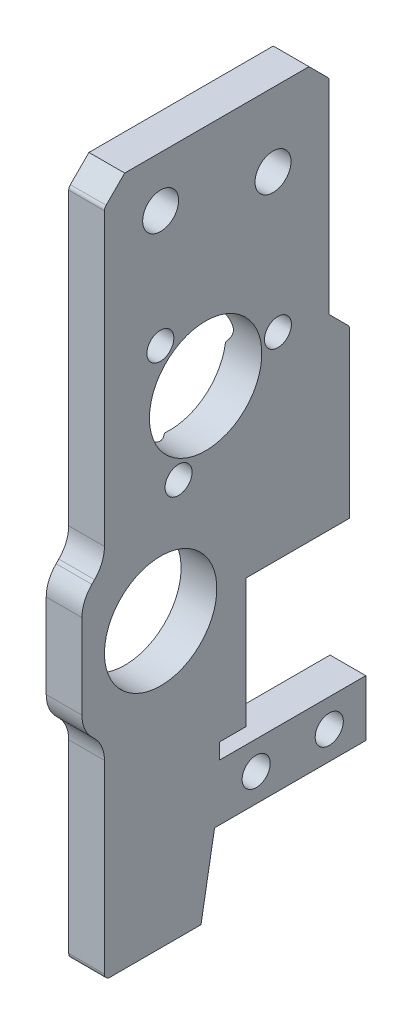
SolidWorks part; units mm, degrees
ref_plane "Front Plane" through (0, 0, 0) normal (0, 0, 1) x (1, 0, 0)
ref_plane "Top Plane" through (0, 0, 0) normal (0, 1, 0) x (1, 0, 0)
ref_plane "Right Plane" through (0, 0, 0) normal (1, 0, 0) x (0, 0, -1)
sketch "Sketch1" plane through (0, 0, 0) normal (1, 0, 0) x (0, 0, -1)
  line L0 (0, 0) -> (0, 18.2)
  line L1 (0, 18.2) -> (-2, 20.2)
  line L2 (-2, 20.2) -> (-2, 30.2)
  line L3 (-2, 30.2) -> (0, 32.2)
  line L4 (0, 32.2) -> (0, 61.31)
  line L5 (0, 61.31) -> (20, 61.31)
  line L7 (21.8, 24.71) -> (12.6, 24.71)
  line L8 (10.25, 13.26) -> (10.25, 11.86)
  line L9 (10.25, 11.86) -> (23.25, 11.86)
  line L10 (23.25, 11.86) -> (23.25, 6.86)
  line L11 (23.25, 6.86) -> (10, 6.86)
  line L12 (10, 6.86) -> (10, 0)
  line L13 (10, 0) -> (0, 0)
  line L14 (-8.9356, -4) -> (60.4069, -4) construction
  line L15 (5, 30.2) -> (-2, 30.2) construction
  line L16 (5, 20.2) -> (-2, 20.2) construction
  line L17 (0, 18.2) -> (0, 32.2) construction
  line L18 (10.25, 13.26) -> (12.6, 13.26)
  line L19 (12.6, 13.26) -> (12.6, 24.71)
  line L23 (20, 61.31) -> (20, 41.31)
  line L24 (20, 41.31) -> (21.8, 41.31)
  line L25 (21.8, 41.31) -> (21.8, 24.71)
  circle A0 centre (5, 25.2) radius 5
  circle A1 centre (5, 56.81) radius 1.6
  circle A2 centre (15, 54.81) radius 1.6
  circle A3 centre (20, 9.36) radius 1.25
  circle A4 centre (13.5, 9.36) radius 1.25
  point P9 (0, 0)
  point P12 (5, 0)
  point P35 (0, 0)
  dimension "D11" = 10
  dimension "D13" = 3.2
  dimension "D17" = 5
  dimension "D21" = 2.5
  dimension "D2" = 61.31
  dimension "D3" = 10.86
  dimension "D4" = 5
  dimension "D5" = 12.85
  dimension "D6" = 13
  dimension "D7" = 10
  dimension "D8" = 4
  dimension "D9" = 2
  dimension "D10" = 2
  dimension "D12" = 29.2
  dimension "D14" = 6.5
  dimension "D15" = 4.5
  dimension "D16" = 5
  dimension "D18" = 6.5
  dimension "D19" = 3.25
  dimension "D20" = 2.5
  dimension "D22" = 1.4
  dimension "D23" = 2.35
  dimension "D24" = 20
  dimension "D25" = 13.25
  dimension "D26" = 1.8
  dimension "D27" = 20
extrude "Boss-Extrude1" add sketch "Sketch1" along normal blind 3.18
chamfer "Chamfer1" distance 8 angle 10 1 edges at (1.59, 0, -10) first distance on face at (1.59, 3.43, -10)
fillet "Fillet1" [suppressed] radius 1
sketch "Sketch3" plane through (0, 0, 0) normal (-1, 0, 0) x (0, 0, 1)
  line L1 (-15.4326, 42.2448) -> (-4.9749, 46.4147) construction
  line L2 (-4.9749, 46.4147) -> (-6.5925, 35.2732) construction
  line L3 (-6.5925, 35.2732) -> (-15.4326, 42.2448) construction
  line L4 (0, 61.31) -> (0, 32.2) construction
  circle A0 centre (-9, 41.3109) radius 5
  circle A2 centre (-9, 41.3109) radius 6.5 construction
  circle A3 centre (-4.9749, 46.4147) radius 1.2 construction
  circle A4 centre (-6.5925, 35.2732) radius 1.2 construction
  circle A5 centre (-15.4326, 42.2448) radius 1.2 construction
  circle A6 centre (-5, 25.2) radius 5 construction
  point P2 (0, 0)
  point P3 (-8.8003, 40.81)
  dimension "D1" = 10
  dimension "D3" = 16.6
  dimension "D4" = 13
  dimension "D5" = 2.4
  dimension "D2" = 9
hole_wizard "CSK for M2 Flat Head Machine Screw1" positions "Sketch6" profile "Sketch7" countersink size "M2" standard "ANSI Metric"
sketch "Sketch6" plane through (0, 0, 0) normal (-1, 0, 0) x (0, 0, 1)
  point P0 (-4.9749, 46.4147)
  point P3 (-15.4326, 42.2448)
  point P6 (-6.5925, 35.2732)
sketch "Sketch7" plane through (0, 46.4147, -4.9749) normal (0, 1, 0) x (0, 0, 1)
  line L0 (0, 0) -> (0, 4.23)
  line L1 (0, 4.23) -> (1.2, 3.509)
  line L2 (1.2, 3.509) -> (1.2, 1)
  line L3 (1.2, 1) -> (2.2, 0)
  line L5 (2.2, 0) -> (0, 0)
  line L6 (-1.2, 1) -> (-2.2, 0) construction
  line L10 (0, 4.23) -> (-1.2, 3.509) construction
  line L11 (0, -6.35) -> (0, 107.95) construction
  dimension "Hole Dia." = 2.4
  dimension "Hole Depth" = 4.23
  dimension "Near C'Sink Dia." = 4.4
  dimension "Near C'Sink Angle" = 90
  dimension "Drill Angle" = 118
extrude "Cut-Extrude4" cut sketch "Sketch3" against normal through all
sketch "Sketch8" [suppressed] plane through (3.18, 0, 0) normal (1, 0, 0) x (0, 0, -1)
  line L0 (0, 60.81) -> (0, 31.7) construction
  line L1 (9, 40.8109) -> (0, 40.8109) construction
  line L2 (0, 43.8109) -> (2.1261, 43.8109)
  line L3 (2.1261, 37.8109) -> (0, 37.8109)
  line L4 (0, 37.8109) -> (0, 43.8109)
  arc A0 (2.1261, 37.8109) -> (2.1261, 43.8109) centre (9, 40.8109) ccw
  circle A1 centre (5, 24.7) radius 5 construction
  point P11 (0, 40.8109)
  dimension "D1" = 16.6
  dimension "D2" = 15
  dimension "D3" = 9
  dimension "D4" = 6
extrude "Cut-Extrude5" [suppressed] cut sketch "Sketch8" against normal through all
fillet "Fillet2" radius 3 4 edges at (1.59, 18.2, 0) (1.59, 20.2, 2) (1.59, 30.2, 2) (1.59, 32.2, 0)
fillet "Chamfer2" radius 1.8 3 edges at (1.59, 61.31, -20) (1.59, 61.31, 0) (1.59, 41.31, -21.8) profile chamfer
fillet "Fillet4" radius 0.5 4 edges at (1.59, 59.51, 0) (1.59, 0, 0) (1.59, 59.51, -20) (1.59, 39.51, -21.8)
